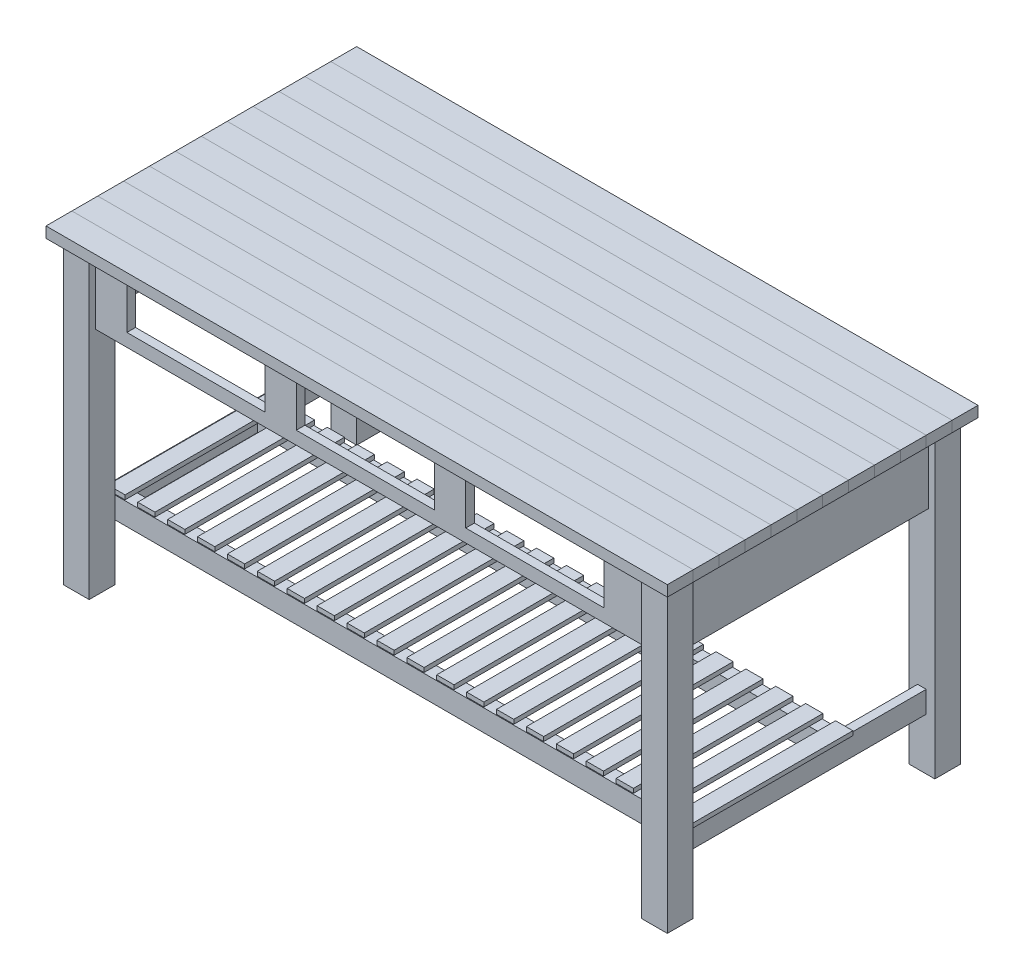
SolidWorks part; units mm, degrees
ref_plane "Default Plane" through (0, 31.75, 0) normal (0, -1, 0) x (-1, 0, 0)
sketch3d "Bounding-Box_Cut-List-Item1"
  line L0 (-914.4, -62.271, 0) -> (914.4, -62.271, 0) construction
  line L1 (914.4, -62.271, 0) -> (914.4, -138.471, 0) construction
  line L2 (914.4, -138.471, 0) -> (-914.4, -138.471, 0) construction
  line L3 (-914.4, -138.471, 0) -> (-914.4, -62.271, 0) construction
  line L4 (-914.4, -62.271, 31.75) -> (914.4, -62.271, 31.75) construction
  line L5 (914.4, -62.271, 31.75) -> (914.4, -138.471, 31.75) construction
  line L6 (914.4, -138.471, 31.75) -> (-914.4, -138.471, 31.75) construction
  line L7 (-914.4, -138.471, 31.75) -> (-914.4, -62.271, 31.75) construction
  line L8 (-914.4, -62.271, 0) -> (-914.4, -62.271, 31.75) construction
  line L9 (914.4, -62.271, 0) -> (914.4, -62.271, 31.75) construction
  line L10 (914.4, -138.471, 0) -> (914.4, -138.471, 31.75) construction
  line L11 (-914.4, -138.471, 0) -> (-914.4, -138.471, 31.75) construction
ref_plane "Default Plane" through (889, 0, -750.529) normal (-1, 0, 0) x (0, 0, 1)
sketch3d "Bounding-Box_Cut-List-Item4"
  line L0 (76.2, 0, 0) -> (76.2, -882.65, 0) construction
  line L1 (76.2, -882.65, 0) -> (0, -882.65, 0) construction
  line L2 (0, -882.65, 0) -> (0, 0, 0) construction
  line L3 (0, 0, 0) -> (76.2, 0, 0) construction
  line L4 (76.2, 0, 76.2) -> (76.2, -882.65, 76.2) construction
  line L5 (76.2, -882.65, 76.2) -> (0, -882.65, 76.2) construction
  line L6 (0, -882.65, 76.2) -> (0, 0, 76.2) construction
  line L7 (0, 0, 76.2) -> (76.2, 0, 76.2) construction
  line L8 (76.2, 0, 0) -> (76.2, 0, 76.2) construction
  line L9 (76.2, -882.65, 0) -> (76.2, -882.65, 76.2) construction
  line L10 (0, -882.65, 0) -> (0, -882.65, 76.2) construction
  line L11 (0, 0, 0) -> (0, 0, 76.2) construction
ref_plane "Default Plane" through (863.6, -666.75, -674.329) normal (-1, 0, 0) x (0, 0, 1)
sketch3d "Bounding-Box_Cut-List-Item5"
  line L0 (0, -63.5, 0) -> (711.2, -63.5, 0) construction
  line L1 (711.2, -63.5, 0) -> (711.2, 0, 0) construction
  line L2 (711.2, 0, 0) -> (0, 0, 0) construction
  line L3 (0, 0, 0) -> (0, -63.5, 0) construction
  line L4 (0, -63.5, 25.4) -> (711.2, -63.5, 25.4) construction
  line L5 (711.2, -63.5, 25.4) -> (711.2, 0, 25.4) construction
  line L6 (711.2, 0, 25.4) -> (0, 0, 25.4) construction
  line L7 (0, 0, 25.4) -> (0, -63.5, 25.4) construction
  line L8 (0, -63.5, 0) -> (0, -63.5, 25.4) construction
  line L9 (711.2, -63.5, 0) -> (711.2, -63.5, 25.4) construction
  line L10 (711.2, 0, 0) -> (711.2, 0, 25.4) construction
  line L11 (0, 0, 0) -> (0, 0, 25.4) construction
ref_plane "Default Plane" through (-812.8, 0, -750.529) normal (-1, 0, 0) x (0, 0, 1)
sketch3d "Bounding-Box_Cut-List-Item6"
  line L0 (863.6, 0, 0) -> (863.6, -882.65, 0) construction
  line L1 (863.6, -882.65, 0) -> (0, -882.65, 0) construction
  line L2 (0, -882.65, 0) -> (0, 0, 0) construction
  line L3 (0, 0, 0) -> (863.6, 0, 0) construction
  line L4 (863.6, 0, 76.2) -> (863.6, -882.65, 76.2) construction
  line L5 (863.6, -882.65, 76.2) -> (0, -882.65, 76.2) construction
  line L6 (0, -882.65, 76.2) -> (0, 0, 76.2) construction
  line L7 (0, 0, 76.2) -> (863.6, 0, 76.2) construction
  line L8 (863.6, 0, 0) -> (863.6, 0, 76.2) construction
  line L9 (863.6, -882.65, 0) -> (863.6, -882.65, 76.2) construction
  line L10 (0, -882.65, 0) -> (0, -882.65, 76.2) construction
  line L11 (0, 0, 0) -> (0, 0, 76.2) construction
material "Beech"
ref_plane "Front Plane" through (0, 0, 0) normal (0, 0, 1) x (1, 0, 0)
ref_plane "Top Plane" through (0, 0, 0) normal (0, 1, 0) x (1, 0, 0)
ref_plane "Right Plane" through (0, 0, 0) normal (1, 0, 0) x (0, 0, -1)
sketch "Sketch1" plane through (0, 0, 0) normal (0, 1, 0) x (1, 0, 0)
  line L0 (0, -450.3596) -> (0, 450.3596) construction
  line L1 (-914.4, -62.271) -> (914.4, -62.271)
  line L2 (-914.4, -62.271) -> (-914.4, -138.471)
  line L3 (-914.4, -138.471) -> (914.4, -138.471)
  line L4 (914.4, -62.271) -> (914.4, -138.471)
  line L6 (-914.4, -62.271) -> (914.4, -62.271)
  line L7 (-914.4, -62.271) -> (-914.4, 13.929)
  line L8 (-914.4, 13.929) -> (914.4, 13.929)
  line L9 (914.4, -62.271) -> (914.4, 13.929)
  line L10 (-914.4, 13.929) -> (914.4, 13.929)
  line L11 (-914.4, 13.929) -> (-914.4, 90.129)
  line L12 (-914.4, 90.129) -> (914.4, 90.129)
  line L13 (914.4, 13.929) -> (914.4, 90.129)
  line L14 (-914.4, 90.129) -> (914.4, 90.129)
  line L15 (-914.4, 90.129) -> (-914.4, 166.329)
  line L16 (-914.4, 166.329) -> (914.4, 166.329)
  line L17 (914.4, 90.129) -> (914.4, 166.329)
  line L18 (-914.4, 166.329) -> (914.4, 166.329)
  line L19 (-914.4, 166.329) -> (-914.4, 242.529)
  line L20 (-914.4, 242.529) -> (914.4, 242.529)
  line L21 (914.4, 166.329) -> (914.4, 242.529)
  line L22 (-914.4, 242.529) -> (914.4, 242.529)
  line L23 (-914.4, 242.529) -> (-914.4, 318.729)
  line L24 (-914.4, 318.729) -> (914.4, 318.729)
  line L25 (914.4, 242.529) -> (914.4, 318.729)
  line L26 (-914.4, 318.729) -> (914.4, 318.729)
  line L27 (-914.4, 318.729) -> (-914.4, 394.929)
  line L28 (-914.4, 394.929) -> (914.4, 394.929)
  line L29 (914.4, 318.729) -> (914.4, 394.929)
  line L30 (-914.4, 394.929) -> (914.4, 394.929)
  line L31 (-914.4, 394.929) -> (-914.4, 471.129)
  line L32 (-914.4, 471.129) -> (914.4, 471.129)
  line L33 (914.4, 394.929) -> (914.4, 471.129)
  line L34 (-914.4, 471.129) -> (914.4, 471.129)
  line L35 (-914.4, 471.129) -> (-914.4, 547.329)
  line L36 (-914.4, 547.329) -> (914.4, 547.329)
  line L37 (914.4, 471.129) -> (914.4, 547.329)
  line L38 (-914.4, 547.329) -> (914.4, 547.329)
  line L39 (-914.4, 547.329) -> (-914.4, 623.529)
  line L40 (-914.4, 623.529) -> (914.4, 623.529)
  line L41 (914.4, 547.329) -> (914.4, 623.529)
  line L42 (-914.4, 623.529) -> (914.4, 623.529)
  line L43 (-914.4, 623.529) -> (-914.4, 699.729)
  line L44 (-914.4, 699.729) -> (914.4, 699.729)
  line L45 (914.4, 623.529) -> (914.4, 699.729)
  line L46 (914.4, -138.471) -> (-914.4, -138.471)
  line L47 (-914.4, 699.729) -> (914.4, 699.729)
  line L48 (-914.4, 699.729) -> (-914.4, 775.929)
  line L49 (-914.4, 775.929) -> (914.4, 775.929)
  line L50 (914.4, 699.729) -> (914.4, 775.929)
  dimension "D1" = 76.2
  dimension "D2" = 1828.8
  dimension "D3" = 914.4
  dimension "D4" = 76.2
extrude "top1" add sketch "Sketch1" along normal blind 31.75 contours L4 L1 L2 L3 region at (0, 0, 100.371)
extrude "top2" add sketch "Sketch1<9>" along normal blind 31.75 separate body contours L1 L9 L8 L7 region at (0, 0, 24.171)
sketch "Sketch1<9>" plane through (0, 0, 0) normal (0, 1, 0) x (1, 0, 0) same geometry as "Sketch1"
extrude "top3" add sketch "Sketch1<10>" along normal blind 31.75 separate body contours L8 L13 L12 L11 region at (0, 0, -52.029)
sketch "Sketch1<10>" plane through (0, 0, 0) normal (0, 1, 0) x (1, 0, 0) same geometry as "Sketch1"
extrude "top4" add sketch "Sketch1<11>" along normal blind 31.75 separate body contours L12 L17 L16 L15 region at (0, 0, -128.229)
sketch "Sketch1<11>" plane through (0, 0, 0) normal (0, 1, 0) x (1, 0, 0) same geometry as "Sketch1"
extrude "top5" add sketch "Sketch1<12>" along normal blind 31.75 separate body contours L16 L21 L20 L19 region at (0, 0, -204.429)
sketch "Sketch1<12>" plane through (0, 0, 0) normal (0, 1, 0) x (1, 0, 0) same geometry as "Sketch1"
extrude "top6" add sketch "Sketch1<13>" along normal blind 31.75 separate body contours L20 L25 L24 L23 region at (0, 0, -280.629)
sketch "Sketch1<13>" plane through (0, 0, 0) normal (0, 1, 0) x (1, 0, 0) same geometry as "Sketch1"
extrude "top7" add sketch "Sketch1<14>" along normal blind 31.75 separate body contours L24 L29 L28 L27 region at (0, 0, -356.829)
sketch "Sketch1<14>" plane through (0, 0, 0) normal (0, 1, 0) x (1, 0, 0) same geometry as "Sketch1"
extrude "top8" add sketch "Sketch1<15>" along normal blind 31.75 separate body contours L28 L33 L32 L31 region at (0, 0, -433.029)
sketch "Sketch1<15>" plane through (0, 0, 0) normal (0, 1, 0) x (1, 0, 0) same geometry as "Sketch1"
extrude "top9" add sketch "Sketch1<16>" along normal blind 31.75 separate body contours L32 L37 L36 L35 region at (0, 0, -509.229)
sketch "Sketch1<16>" plane through (0, 0, 0) normal (0, 1, 0) x (1, 0, 0) same geometry as "Sketch1"
extrude "top10" add sketch "Sketch1<17>" along normal blind 31.75 separate body contours L36 L41 L40 L39 region at (0, 0, -585.429)
sketch "Sketch1<17>" plane through (0, 0, 0) normal (0, 1, 0) x (1, 0, 0) same geometry as "Sketch1"
extrude "top11" add sketch "Sketch1<19>" along normal blind 31.75 separate body contours L40 L45 L44 L43 region at (0, 0, -661.629)
sketch "Sketch1<19>" plane through (0, 0, 0) normal (0, 1, 0) x (1, 0, 0) same geometry as "Sketch1"
extrude "top12" add sketch "Sketch1<20>" along normal blind 31.75 separate body contours L3 L49 region at (0, 0, -737.829)
sketch "Sketch1<20>" plane through (0, 0, 0) normal (0, 1, 0) x (1, 0, 0) same geometry as "Sketch1"
sketch "Sketch2" plane through (0, 0, 0) normal (0, 1, 0) x (1, 0, 0)
  line L0 (-914.4, 699.729) -> (-914.4, 775.929) construction
  line L1 (-889, -113.071) -> (-812.8, -113.071)
  line L2 (-889, -113.071) -> (-889, -36.871)
  line L3 (-889, -36.871) -> (-812.8, -36.871)
  line L4 (-812.8, -113.071) -> (-812.8, -36.871)
  line L5 (-889, 674.329) -> (-812.8, 674.329)
  line L6 (-889, 674.329) -> (-889, 750.529)
  line L7 (-889, 750.529) -> (-812.8, 750.529)
  line L8 (-812.8, 674.329) -> (-812.8, 750.529)
  line L10 (0, -1000) -> (0, 49000) construction
  line L11 (812.8, 674.329) -> (812.8, 750.529)
  line L12 (889, 750.529) -> (812.8, 750.529)
  line L13 (889, 674.329) -> (889, 750.529)
  line L14 (889, 674.329) -> (812.8, 674.329)
  line L15 (812.8, -113.071) -> (812.8, -36.871)
  line L16 (889, -36.871) -> (812.8, -36.871)
  line L17 (889, -113.071) -> (889, -36.871)
  line L18 (889, -113.071) -> (812.8, -113.071)
  line L20 (-914.4, 775.929) -> (914.4, 775.929) construction
  dimension "D1" = 76.2
  dimension "D2" = 76.2
  dimension "D3" = 25.4
  dimension "D4" = 25.4
extrude "table legs" add sketch "Sketch2" against normal blind 882.65 separate body
ref_plane "Plane6" through (0, 0, -674.329) normal (0, 0, 1) x (1, 0, 0)
sketch "Sketch4" plane through (0, 0, -674.329) normal (0, 0, 1) x (1, 0, 0)
  line L0 (812.8, -882.65) -> (889, -882.65) construction
  line L1 (838.2, -666.75) -> (863.6, -666.75)
  line L2 (838.2, -666.75) -> (838.2, -730.25)
  line L3 (838.2, -730.25) -> (863.6, -730.25)
  line L4 (863.6, -666.75) -> (863.6, -730.25)
  line L5 (812.8, -882.65) -> (812.8, 0) construction
  line L6 (889, -882.65) -> (889, 0) construction
  point P4 (850.9, -882.65)
  dimension "D1" = 152.4
  dimension "D2" = 25.4
  dimension "D3" = 63.5
  dimension "D4" = 25.4
extrude "stretcher width" add sketch "Sketch4" along normal up to surface (711.2 mm away) separate body up to face at (850.9, -441.325, 36.871)
mirror "Mirror4" about plane through (0, 0, 0) normal (1, 0, 0) of "stretcher width"
ref_plane "Plane7" through (-838.2, 0, 0) normal (1, 0, 0) x (0, 0, -1)
sketch "Sketch5" plane through (-838.2, 0, 0) normal (1, 0, 0) x (0, 0, -1)
  line L1 (-36.871, -666.75) -> (674.329, -666.75) construction
  line L2 (-24.171, -666.75) -> (13.929, -666.75)
  line L3 (-24.171, -666.75) -> (-24.171, -730.25)
  line L4 (-24.171, -730.25) -> (13.929, -730.25)
  line L5 (13.929, -666.75) -> (13.929, -730.25)
  line L6 (-36.871, -730.25) -> (674.329, -730.25) construction
  line L7 (-36.871, -882.65) -> (-36.871, 0) construction
  line L8 (674.329, -666.75) -> (674.329, -730.25) construction
  line L9 (445.729, -666.75) -> (407.629, -666.75)
  line L10 (445.729, -666.75) -> (445.729, -730.25)
  line L11 (445.729, -730.25) -> (407.629, -730.25)
  line L12 (407.629, -666.75) -> (407.629, -730.25)
  dimension "D1" = 12.7
  dimension "D2" = 38.1
  dimension "D3" = 228.6
  dimension "D4" = 38.1
ref_plane "Plane8" through (0, 0, -280.629) normal (0, 0, -1) x (-1, 0, 0)
extrude "stretcher length" add sketch "Sketch5" along normal up to surface (1676.4 mm away) separate body up to face at (838.2, -698.5, -318.729)
ref_plane "Plane9" through (-812.8, 0, 0) normal (1, 0, 0) x (0, 0, -1)
sketch "Sketch7" plane through (-812.8, 0, 0) normal (1, 0, 0) x (0, 0, -1)
  line L0 (-113.071, 0) -> (-36.871, 0) construction
  line L1 (-94.021, 0) -> (-68.621, 0)
  line L2 (-94.021, 0) -> (-94.021, -203.2)
  line L3 (-94.021, -203.2) -> (-68.621, -203.2)
  line L4 (-68.621, 0) -> (-68.621, -203.2)
  line L5 (-113.071, -882.65) -> (-113.071, 0) construction
  dimension "D1" = 19.05
  dimension "D2" = 25.4
  dimension "D3" = 203.2
extrude "front face plate" add sketch "Sketch7" along normal up to surface (1625.6 mm away) separate body up to face at (812.8, -441.325, 74.971)
sketch "Sketch8" plane through (0, 0, -674.329) normal (0, 0, 1) x (1, 0, 0)
  line L0 (812.8, 0) -> (889, 0) construction
  line L1 (869.95, 0) -> (844.55, 0)
  line L2 (869.95, 0) -> (869.95, -203.2)
  line L3 (869.95, -203.2) -> (844.55, -203.2)
  line L4 (844.55, 0) -> (844.55, -203.2)
  line L5 (889, -882.65) -> (889, 0) construction
  line L6 (-889, 0) -> (-812.8, 0) construction
  line L7 (-869.95, 0) -> (-844.55, 0)
  line L8 (-869.95, 0) -> (-869.95, -203.2)
  line L9 (-869.95, -203.2) -> (-844.55, -203.2)
  line L10 (-844.55, 0) -> (-844.55, -203.2)
  line L11 (-889, -882.65) -> (-889, 0) construction
  dimension "D1" = 19.05
  dimension "D2" = 25.4
  dimension "D3" = 203.2
  dimension "D4" = 19.05
  dimension "D5" = 25.4
  dimension "D6" = 203.2
extrude "side face plates" add sketch "Sketch8" along normal up to surface (711.2 mm away) separate body up to face at (-850.9, -441.325, 36.871)
ref_plane "Plane10" through (0, 0, -445.729) normal (0, 0, -1) x (-1, 0, 0)
sketch "Sketch9" plane through (0, 0, -445.729) normal (0, 0, -1) x (-1, 0, 0)
  line L0 (-788.2167, -664.4034) -> (-737.4167, -664.4034)
  line L1 (-876.2277, -664.4034) -> (-825.4277, -664.4034)
  line L2 (-876.2277, -664.4034) -> (-876.2277, -651.7034)
  line L3 (-876.2277, -651.7034) -> (-825.4277, -651.7034)
  line L4 (-825.4277, -664.4034) -> (-825.4277, -651.7034)
  line L5 (-788.2167, -664.4034) -> (-788.2167, -651.7034)
  line L6 (-788.2167, -651.7034) -> (-737.4167, -651.7034)
  line L7 (-737.4167, -664.4034) -> (-737.4167, -651.7034)
  line L8 (-700.2057, -664.4034) -> (-649.4057, -664.4034)
  line L9 (-700.2057, -664.4034) -> (-700.2057, -651.7034)
  line L10 (-700.2057, -651.7034) -> (-649.4057, -651.7034)
  line L11 (-649.4057, -664.4034) -> (-649.4057, -651.7034)
  line L12 (-612.1947, -664.4034) -> (-561.3947, -664.4034)
  line L13 (-612.1947, -664.4034) -> (-612.1947, -651.7034)
  line L14 (-612.1947, -651.7034) -> (-561.3947, -651.7034)
  line L15 (-561.3947, -664.4034) -> (-561.3947, -651.7034)
  line L16 (-524.1837, -664.4034) -> (-473.3837, -664.4034)
  line L17 (-524.1837, -664.4034) -> (-524.1837, -651.7034)
  line L18 (-524.1837, -651.7034) -> (-473.3837, -651.7034)
  line L19 (-473.3837, -664.4034) -> (-473.3837, -651.7034)
  line L20 (-436.1727, -664.4034) -> (-385.3727, -664.4034)
  line L21 (-436.1727, -664.4034) -> (-436.1727, -651.7034)
  line L22 (-436.1727, -651.7034) -> (-385.3727, -651.7034)
  line L23 (-385.3727, -664.4034) -> (-385.3727, -651.7034)
  line L24 (-348.1617, -664.4034) -> (-297.3617, -664.4034)
  line L25 (-348.1617, -664.4034) -> (-348.1617, -651.7034)
  line L26 (-348.1617, -651.7034) -> (-297.3617, -651.7034)
  line L27 (-297.3617, -664.4034) -> (-297.3617, -651.7034)
  line L28 (-260.1507, -664.4034) -> (-209.3507, -664.4034)
  line L29 (-260.1507, -664.4034) -> (-260.1507, -651.7034)
  line L30 (-260.1507, -651.7034) -> (-209.3507, -651.7034)
  line L31 (-209.3507, -664.4034) -> (-209.3507, -651.7034)
  line L32 (-172.1397, -664.4034) -> (-121.3397, -664.4034)
  line L33 (-172.1397, -664.4034) -> (-172.1397, -651.7034)
  line L34 (-172.1397, -651.7034) -> (-121.3397, -651.7034)
  line L35 (-121.3397, -664.4034) -> (-121.3397, -651.7034)
  line L36 (-84.1287, -664.4034) -> (-33.3287, -664.4034)
  line L37 (-84.1287, -664.4034) -> (-84.1287, -651.7034)
  line L38 (-84.1287, -651.7034) -> (-33.3287, -651.7034)
  line L39 (-33.3287, -664.4034) -> (-33.3287, -651.7034)
  line L40 (3.8823, -664.4034) -> (54.6823, -664.4034)
  line L41 (3.8823, -664.4034) -> (3.8823, -651.7034)
  line L42 (3.8823, -651.7034) -> (54.6823, -651.7034)
  line L43 (54.6823, -664.4034) -> (54.6823, -651.7034)
  line L44 (91.8933, -664.4034) -> (142.6933, -664.4034)
  line L45 (91.8933, -664.4034) -> (91.8933, -651.7034)
  line L46 (91.8933, -651.7034) -> (142.6933, -651.7034)
  line L47 (142.6933, -664.4034) -> (142.6933, -651.7034)
  line L48 (179.9043, -664.4034) -> (230.7043, -664.4034)
  line L49 (179.9043, -664.4034) -> (179.9043, -651.7034)
  line L50 (179.9043, -651.7034) -> (230.7043, -651.7034)
  line L51 (230.7043, -664.4034) -> (230.7043, -651.7034)
  line L52 (267.9153, -664.4034) -> (318.7153, -664.4034)
  line L53 (267.9153, -664.4034) -> (267.9153, -651.7034)
  line L54 (267.9153, -651.7034) -> (318.7153, -651.7034)
  line L55 (318.7153, -664.4034) -> (318.7153, -651.7034)
  line L56 (355.9263, -664.4034) -> (406.7263, -664.4034)
  line L57 (355.9263, -664.4034) -> (355.9263, -651.7034)
  line L58 (355.9263, -651.7034) -> (406.7263, -651.7034)
  line L59 (406.7263, -664.4034) -> (406.7263, -651.7034)
  line L60 (443.9373, -664.4034) -> (494.7373, -664.4034)
  line L61 (443.9373, -664.4034) -> (443.9373, -651.7034)
  line L62 (443.9373, -651.7034) -> (494.7373, -651.7034)
  line L63 (494.7373, -664.4034) -> (494.7373, -651.7034)
  line L64 (531.9483, -664.4034) -> (582.7483, -664.4034)
  line L65 (531.9483, -664.4034) -> (531.9483, -651.7034)
  line L66 (531.9483, -651.7034) -> (582.7483, -651.7034)
  line L67 (582.7483, -664.4034) -> (582.7483, -651.7034)
  line L68 (619.9593, -664.4034) -> (670.7593, -664.4034)
  line L69 (619.9593, -664.4034) -> (619.9593, -651.7034)
  line L70 (619.9593, -651.7034) -> (670.7593, -651.7034)
  line L71 (670.7593, -664.4034) -> (670.7593, -651.7034)
  line L72 (707.9703, -664.4034) -> (758.7703, -664.4034)
  line L73 (707.9703, -664.4034) -> (707.9703, -651.7034)
  line L74 (707.9703, -651.7034) -> (758.7703, -651.7034)
  line L75 (758.7703, -664.4034) -> (758.7703, -651.7034)
  line L76 (795.9813, -664.4034) -> (846.7813, -664.4034)
  line L77 (795.9813, -664.4034) -> (795.9813, -651.7034)
  line L78 (795.9813, -651.7034) -> (846.7813, -651.7034)
  line L79 (846.7813, -664.4034) -> (846.7813, -651.7034)
  dimension "D1" = 38.1
  dimension "D2" = 50.8
  dimension "D3" = 12.7
  dimension "D4" = 20
extrude "stretcher rack boards" add sketch "Sketch9" against normal up to surface (469.9 mm away) separate body up to face at (0, -698.5, 24.171)
ref_plane "Plane11" through (0, 0, 94.021) normal (0, 0, 1) x (1, 0, 0)
sketch "Sketch10" plane through (0, 0, 94.021) normal (0, 0, 1) x (1, 0, 0)
  line L0 (-812.8, 0) -> (-812.8, -203.2) construction
  line L1 (-720.725, -38.1) -> (-314.325, -38.1)
  line L2 (-720.725, -38.1) -> (-720.725, -165.1)
  line L3 (-720.725, -165.1) -> (-314.325, -165.1)
  line L4 (-314.325, -38.1) -> (-314.325, -165.1)
  line L5 (812.8, 0) -> (-812.8, 0) construction
  line L6 (812.8, -203.2) -> (-812.8, -203.2) construction
  line L7 (-222.123, -38.1) -> (184.277, -38.1)
  line L8 (-222.123, -38.1) -> (-222.123, -165.1)
  line L9 (-222.123, -165.1) -> (184.277, -165.1)
  line L10 (184.277, -38.1) -> (184.277, -165.1)
  line L11 (276.479, -38.1) -> (682.879, -38.1)
  line L12 (276.479, -38.1) -> (276.479, -165.1)
  line L13 (276.479, -165.1) -> (682.879, -165.1)
  line L14 (682.879, -38.1) -> (682.879, -165.1)
  dimension "D1" = 92.075
  dimension "D2" = 38.1
  dimension "D3" = 38.1
  dimension "D4" = 406.4
  dimension "D5" = 3
extrude "drawer cut outs" cut sketch "Sketch10" against normal up to next (25.4 mm away)
ref_plane "Plane12" through (-812.8, 0, 0) normal (1, 0, 0) x (0, 0, -1)
sketch "Sketch11" plane through (-812.8, 0, 0) normal (1, 0, 0) x (0, 0, -1)
  line L0 (674.329, 0) -> (750.529, 0) construction
  line L1 (731.479, 0) -> (706.079, 0)
  line L2 (731.479, 0) -> (731.479, -101.6)
  line L3 (731.479, -101.6) -> (706.079, -101.6)
  line L4 (706.079, 0) -> (706.079, -101.6)
  line L5 (750.529, -882.65) -> (750.529, 0) construction
  dimension "D1" = 19.05
  dimension "D2" = 101.6
  dimension "D3" = 25.4
extrude "back face plate" add sketch "Sketch11" along normal up to surface (1625.6 mm away) separate body up to face at (812.8, -441.325, -712.429)
equation "\"table_thickness\"=1.25"
equation "\"D1@top1\"=\"table_thickness\""
equation "\"D1@top2\"=\"table_thickness\""
equation "\"D1@top3\"=\"table_thickness\""
equation "\"D1@top4\"=\"table_thickness\""
equation "\"D1@top5\"=\"table_thickness\""
equation "\"D1@top6\"=\"table_thickness\""
equation "\"D1@top7\"=\"table_thickness\""
equation "\"D1@top8\"=\"table_thickness\""
equation "\"D1@top9\"=\"table_thickness\""
equation "\"D1@top10\"=\"table_thickness\""
equation "\"D1@top11\"=\"table_thickness\""
equation "\"D1@top12\"=\"table_thickness\""
